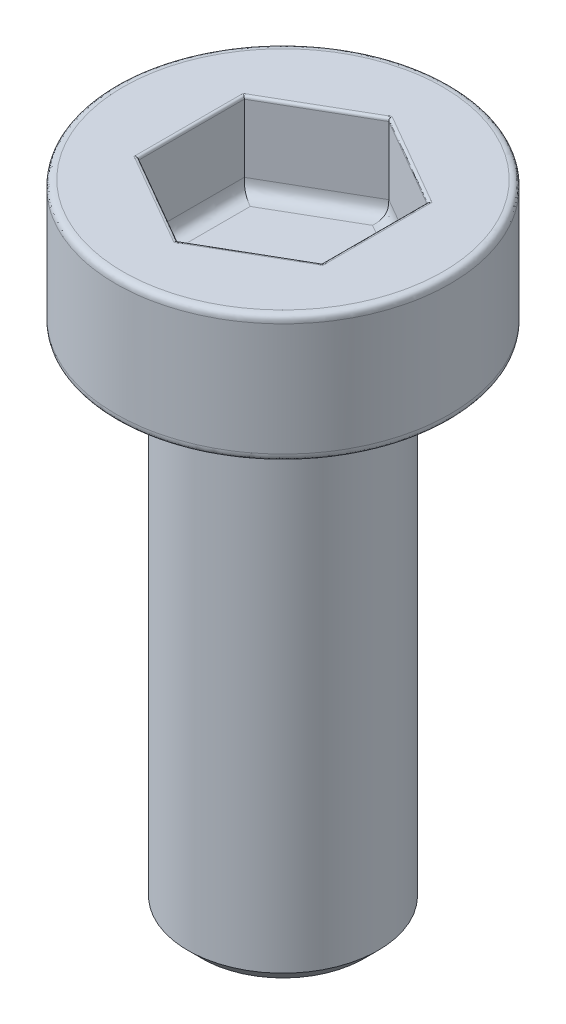
SolidWorks part; units mm, degrees
ref_plane "Front Plane" through (0, 0, 0) normal (0, 0, 1) x (1, 0, 0)
ref_plane "Top Plane" through (0, 0, 0) normal (0, 1, 0) x (1, 0, 0)
ref_plane "Right Plane" through (0, 0, 0) normal (1, 0, 0) x (0, 0, -1)
sketch "Sketch2" plane through (0, 0, 0) normal (1, 0, 0) x (0, 0, -1)
  line L0 (0, 0) -> (0, 45)
  line L1 (0, 45) -> (11.85, 45)
  line L2 (11.85, 45) -> (11.85, 36)
  line L3 (11.85, 36) -> (6.75, 36)
  line L4 (6.75, 36) -> (6.75, 0)
  line L5 (6.75, 0) -> (0, 0)
  dimension "D1" = 6.75
  dimension "D2" = 11.85
  dimension "D3" = 9
  dimension "D4" = 45
revolve "Revolve1" add sketch "Sketch2" angle 360 about L0
chamfer "Chamfer1" distance 1 angle 45 1 edges at (0, 0, -6.75)
sketch "Sketch3" plane through (0, 45, 0) normal (0, 1, 0) x (1, 0, 0)
  line L1 (0, 7.5056) -> (-6.5, 3.7528)
  line L2 (-6.5, 3.7528) -> (-6.5, -3.7528)
  line L3 (-6.5, -3.7528) -> (0, -7.5056)
  line L4 (0, -7.5056) -> (6.5, -3.7528)
  line L5 (6.5, -3.7528) -> (6.5, 3.7528)
  line L6 (6.5, 3.7528) -> (0, 7.5056)
  circle A0 centre (0, 0) radius 6.5 construction
  dimension "D1" = 13
extrude "Cut-Extrude1" cut sketch "Sketch3" against normal blind 6
fillet "Fillet1" radius 1 6 edges at (6.5, 39, 0) (3.25, 39, 5.6292) (-3.25, 39, 5.6292) (-6.5, 39, 0) (-3.25, 39, -5.6292) (3.25, 39, -5.6292) curvature continuous yes
fillet "Fillet2" radius 0.5 2 edges at (0, 36, -11.85) (0, 45, -11.85) curvature continuous yes
ref_axis "Axis1" through (0, 36, 0) along (0, -1, 0)
fillet "Fillet3" radius 0.2 6 edges at (-6.5, 45, 0) (-3.25, 45, 5.6292) (3.25, 45, 5.6292) (6.5, 45, 0) (3.25, 45, -5.6292) (-3.25, 45, -5.6292) curvature continuous yes
